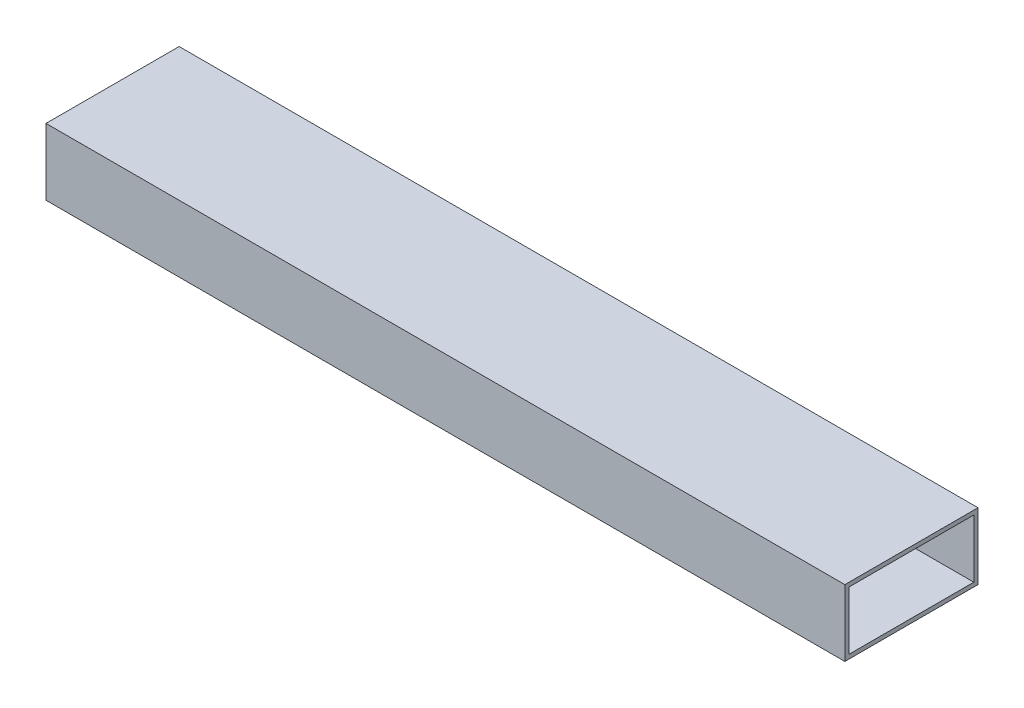
SolidWorks part; units mm, degrees
ref_plane "Front Plane" through (0, 0, 0) normal (0, 0, 1) x (1, 0, 0)
ref_plane "Top Plane" through (0, 0, 0) normal (0, 1, 0) x (1, 0, 0)
ref_plane "Right Plane" through (0, 0, 0) normal (1, 0, 0) x (0, 0, -1)
sketch "Sketch1" plane through (0, 0, 0) normal (1, 0, 0) x (0, 0, -1)
  line L1 (0, 0) -> (50.8, 0)
  line L2 (0, 0) -> (0, 25.4)
  line L3 (0, 25.4) -> (50.8, 25.4)
  line L4 (50.8, 0) -> (50.8, 25.4)
  dimension "D1" = 50.8
  dimension "D2" = 25.4
extrude "Extrude-Thin1" add sketch "Sketch1" along normal blind 304.8 thin thin type one direction reverse wall 1.5875
